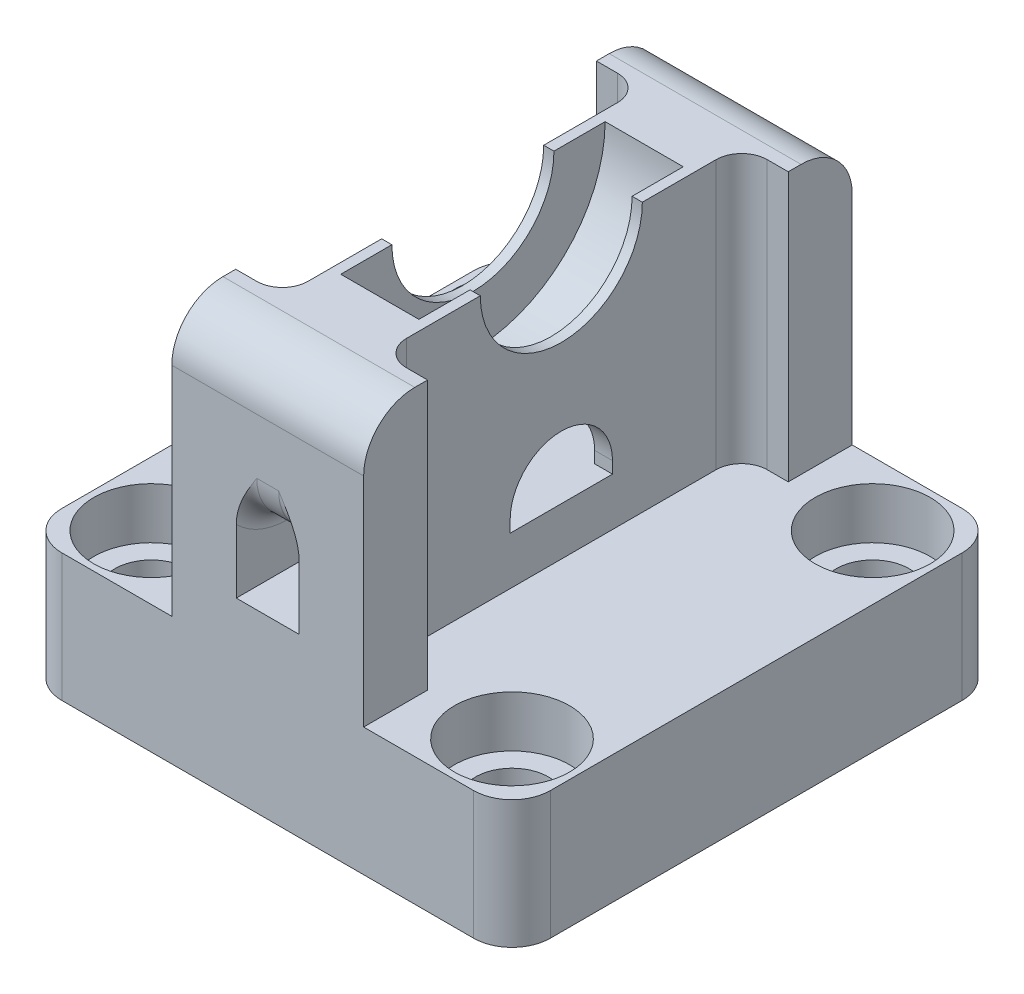
SolidWorks part; units mm, degrees
ref_plane "Front Plane" through (0, 0, 0) normal (0, 0, 1) x (1, 0, 0)
ref_plane "Top Plane" through (0, 0, 0) normal (0, 1, 0) x (1, 0, 0)
ref_plane "Right Plane" through (0, 0, 0) normal (1, 0, 0) x (0, 0, -1)
sketch "Sketch1" plane through (0, 0, 0) normal (0, 1, 0) x (1, 0, 0)
  line L1 (-24.257, -24.257) -> (24.257, -24.257)
  line L2 (-24.257, -24.257) -> (-24.257, 24.257)
  line L3 (-24.257, 24.257) -> (24.257, 24.257)
  line L4 (24.257, -24.257) -> (24.257, 24.257)
  line L5 (-24.257, -24.257) -> (24.257, 24.257) construction
  line L6 (-24.257, 24.257) -> (24.257, -24.257) construction
  circle A0 centre (-17.907, 17.907) radius 3.6195
  circle A1 centre (17.907, 17.907) radius 3.6195
  circle A2 centre (17.907, -17.907) radius 3.6195
  circle A3 centre (-17.907, -17.907) radius 3.6195
  point P0 (0, 0)
  dimension "D2" = 7.239
  dimension "D5" = 6.35
  dimension "D1" = 48.514
  dimension "D3" = 6.35
  dimension "D4" = 6.35
  dimension "D6" = 6.35
extrude "Boss-Extrude1" add sketch "Sketch1" along normal blind 12.7
fillet "Fillet1" radius 3.81 4 edges at (-24.257, 6.35, 24.257) (-24.257, 6.35, -24.257) (24.257, 6.35, -24.257) (24.257, 6.35, 24.257)
sketch "Sketch4" plane through (0, 12.7, 0) normal (0, 1, 0) x (1, 0, 0)
  circle A0 centre (-17.907, 17.907) radius 5.715
  circle A1 centre (17.907, -17.907) radius 5.715
  circle A2 centre (17.907, 17.907) radius 5.715
  circle A3 centre (-17.907, -17.907) radius 5.715
  dimension "D1" = 11.43
extrude "Cut-Extrude2" cut sketch "Sketch4" against normal blind 5.08
sketch "Sketch6" plane through (0, 12.7, 0) normal (0, 1, 0) x (1, 0, 0)
  line L0 (-20.447, -24.257) -> (20.447, -24.257) construction
  line L2 (-3.881, 17.907) -> (-3.881, -17.907)
  line L4 (3.881, 17.907) -> (3.881, -17.907)
  line L5 (-3.048, 24.257) -> (3.048, -24.257) construction
  line L6 (-3.048, -24.257) -> (3.048, 24.257) construction
  line L7 (20.447, 24.257) -> (-20.447, 24.257) construction
  line L8 (-9.525, -24.257) -> (9.525, -24.257)
  line L9 (-9.525, -24.257) -> (-9.525, -17.907)
  line L10 (-9.525, -17.907) -> (-3.881, -17.907)
  line L11 (9.525, -24.257) -> (9.525, -17.907)
  line L12 (-9.525, 24.257) -> (9.525, 24.257)
  line L13 (-9.525, 24.257) -> (-9.525, 17.907)
  line L14 (-9.525, 17.907) -> (-3.881, 17.907)
  line L15 (9.525, 24.257) -> (9.525, 17.907)
  line L16 (3.881, 17.907) -> (9.525, 17.907)
  line L17 (3.881, -17.907) -> (9.525, -17.907)
  line L18 (-3.881, 0) -> (0, 0) construction
  line L19 (0, 0) -> (3.881, 0) construction
  line L20 (3.5, -12.7) -> (3.5, 12.7) construction
  point P0 (0, 0)
  dimension "D1" = 6.096
  dimension "D2" = 6.35
  dimension "D3" = 19.05
  dimension "D4" = 0.381
extrude "Boss-Extrude3" add sketch "Sketch6" along normal blind 26.67
sketch "Sketch7" plane through (0, 0, -24.257) normal (0, 0, -1) x (-1, 0, 0)
  line L0 (-9.525, 39.37) -> (9.525, 39.37) construction
  line L1 (-2.4335, 36.83) -> (2.5195, 36.83)
  line L2 (-2.4335, 36.83) -> (-2.4335, 39.37)
  line L3 (-2.4335, 39.37) -> (2.5195, 39.37)
  line L4 (2.5195, 36.83) -> (2.5195, 39.37)
  line L5 (-2.4335, 36.83) -> (2.5195, 39.37) construction
  line L6 (-2.4335, 39.37) -> (2.5195, 36.83) construction
  point P0 (0.043, 38.1)
  dimension "D1" = 4.953
  dimension "D2" = 2.54
extrude "Cut-Extrude3" [suppressed] cut sketch "Sketch7" against normal up to surface (48.514 mm away)
sketch "Sketch8" plane through (3.881, 0, 0) normal (1, 0, 0) x (0, 0, -1)
  line L0 (-17.907, 39.37) -> (17.907, 39.37) construction
  circle A0 centre (0, 39.37) radius 13.1255
  dimension "D1" = 26.2509
extrude "Cut-Extrude4" cut sketch "Sketch8" against normal up to surface (7.762 mm away) up to face at (-3.881, 26.035, 0)
sketch "Sketch9" plane through (0, 39.37, 0) normal (0, 1, 0) x (1, 0, 0)
  line L0 (3.881, 17.907) -> (9.525, 17.907) construction
  line L1 (9.525, 17.907) -> (9.525, 24.257) construction
  line L2 (-9.525, 24.257) -> (-9.525, 17.907) construction
  line L3 (-9.525, -24.257) -> (9.525, -24.257) construction
  circle A0 centre (6.35, -21.082) radius 1.27
  circle A1 centre (-6.35, -21.082) radius 1.27
  circle A2 centre (-6.35, 21.082) radius 1.27
  circle A3 centre (6.35, 21.082) radius 1.27
  dimension "D1" = 2.54
  dimension "D2" = 3.175
  dimension "D3" = 3.175
  dimension "D4" = 3.175
  dimension "D5" = 3.175
extrude "Cut-Extrude5" [suppressed] cut sketch "Sketch9" against normal blind 6.35
sketch "Sketch11" plane through (0, 0, 24.257) normal (0, 0, 1) x (1, 0, 0)
  line L2 (3.881, 26.2446) -> (3.881, 39.37) construction
  line L4 (3.881, 26.2446) -> (3.881, 39.37) construction
  line L5 (-3.881, 39.37) -> (-3.881, 26.2446) construction
  line L6 (-3.881, 39.37) -> (-3.881, 26.2446) construction
  line L7 (-3.881, 26.2446) -> (3.881, 26.2446) construction
  line L8 (-3.119, 23.7046) -> (3.119, 23.7046)
  line L9 (-3.119, 23.7046) -> (-3.119, 17.4666)
  line L10 (-3.119, 17.4666) -> (3.119, 17.4666)
  line L11 (3.119, 23.7046) -> (3.119, 17.4666)
  line L12 (0, 26.2446) -> (0, 23.7046) construction
  point P9 (2.286, 25.7769)
  point P11 (3.1636, 26.2446)
  dimension "D1" = 0.762
  dimension "D3" = 2.54
extrude "Cut-Extrude7" cut sketch "Sketch11" against normal through all
sketch "Sketch13" plane through (3.881, 0, 0) normal (1, 0, 0) x (0, 0, -1)
  line L0 (0, 23.7046) -> (0, 0) construction
  line L1 (-5.08, 23.7046) -> (-5.08, 0)
  line L2 (5.08, 23.7046) -> (5.08, 0)
  line L4 (-24.257, 23.7046) -> (-24.257, 17.4666)
  line L5 (-24.257, 17.4666) -> (24.257, 17.4666)
  line L6 (24.257, 17.4666) -> (24.257, 23.7046)
  line L7 (24.257, 23.7046) -> (-24.257, 23.7046)
  line L8 (-24.257, 23.7046) -> (-24.257, 17.4666)
  line L9 (-24.257, 17.4666) -> (24.257, 17.4666)
  line L10 (24.257, 17.4666) -> (24.257, 23.7046)
  line L11 (24.257, 23.7046) -> (-24.257, 23.7046)
  dimension "D1" = 0
  dimension "D2" = 5.08
  dimension "D3" = 5.08
extrude "Cut-Extrude8" cut sketch "Sketch13" against normal through all contours L0 L11 L1 L9 | L11 L0 L9 L2 region at (3.881, 20.5856, -2.54) region at (3.881, 20.5856, 2.54)
sketch "Sketch14" plane through (3.881, 0, 0) normal (1, 0, 0) x (0, 0, -1)
  line L5 (17.907, 39.37) -> (13.1254, 39.37)
  line L6 (-13.1254, 39.37) -> (-17.907, 39.37)
  line L7 (-17.907, 39.37) -> (-17.907, 12.7)
  line L8 (-17.907, 12.7) -> (17.907, 12.7)
  line L9 (17.907, 12.7) -> (17.907, 39.37)
  line L10 (17.907, 39.37) -> (8.0454, 39.37)
  line L11 (-8.0454, 39.37) -> (-17.907, 39.37)
  line L12 (-17.907, 39.37) -> (-17.907, 12.7)
  line L13 (-17.907, 12.7) -> (17.907, 12.7)
  line L14 (17.907, 12.7) -> (17.907, 39.37)
  line L15 (5.08, 17.4666) -> (5.08, 23.7046)
  line L16 (-5.08, 17.4666) -> (5.08, 17.4666)
  line L17 (-5.08, 23.7046) -> (-5.08, 17.4666)
  line L18 (5.08, 23.7046) -> (-5.08, 23.7046)
  line L19 (5.08, 17.4666) -> (5.08, 23.7046)
  line L20 (-5.08, 17.4666) -> (5.08, 17.4666)
  line L21 (-5.08, 23.7046) -> (-5.08, 17.4666)
  line L22 (5.08, 23.7046) -> (-5.08, 23.7046)
  arc A0 (-8.0454, 39.37) -> (8.0454, 39.37) centre (0, 39.37) ccw
  arc A1 (-13.1254, 39.37) -> (13.1254, 39.37) centre (0, 39.37) ccw
  arc A2 (-13.1254, 39.37) -> (13.1254, 39.37) centre (0, 39.37) ccw construction
  dimension "D1" = 0
  dimension "D2" = 0
  dimension "D3" = 5.08
extrude "Boss-Extrude4" add sketch "Sketch14" along normal blind 1.016
mirror "Mirror1" about plane through (0, 0, 0) normal (1, 0, 0) of "Boss-Extrude4"
fillet "Fillet3" radius 5.08 4 edges at (0, 39.37, 24.257) (0, 39.37, -24.257) (0, 23.7046, -24.257) (0, 23.7046, 24.257)
fillet "Fillet2" radius 2.54 4 edges at (4.897, 26.035, -17.907) (-4.897, 26.035, -17.907) (-4.897, 26.035, 17.907) (4.897, 26.035, 17.907)
fillet "Fillet4" radius 2.032 8 edges at (-3.119, 25.1924, 22.7691) (-3.119, 23.7046, -12.1285) (-3.119, 23.7046, 12.1285) (3.119, 25.1924, 22.7691) (3.119, 23.7046, -12.1285) (3.119, 23.7046, 12.1285) (-3.119, 25.1924, -22.7691) (3.119, 25.1924, -22.7691)
fillet "Fillet6" radius 5.08 4 edges at (-2.992, 23.7046, -5.08) (2.992, 23.7046, -5.08) (-2.992, 23.7046, 5.08) (2.992, 23.7046, 5.08)
